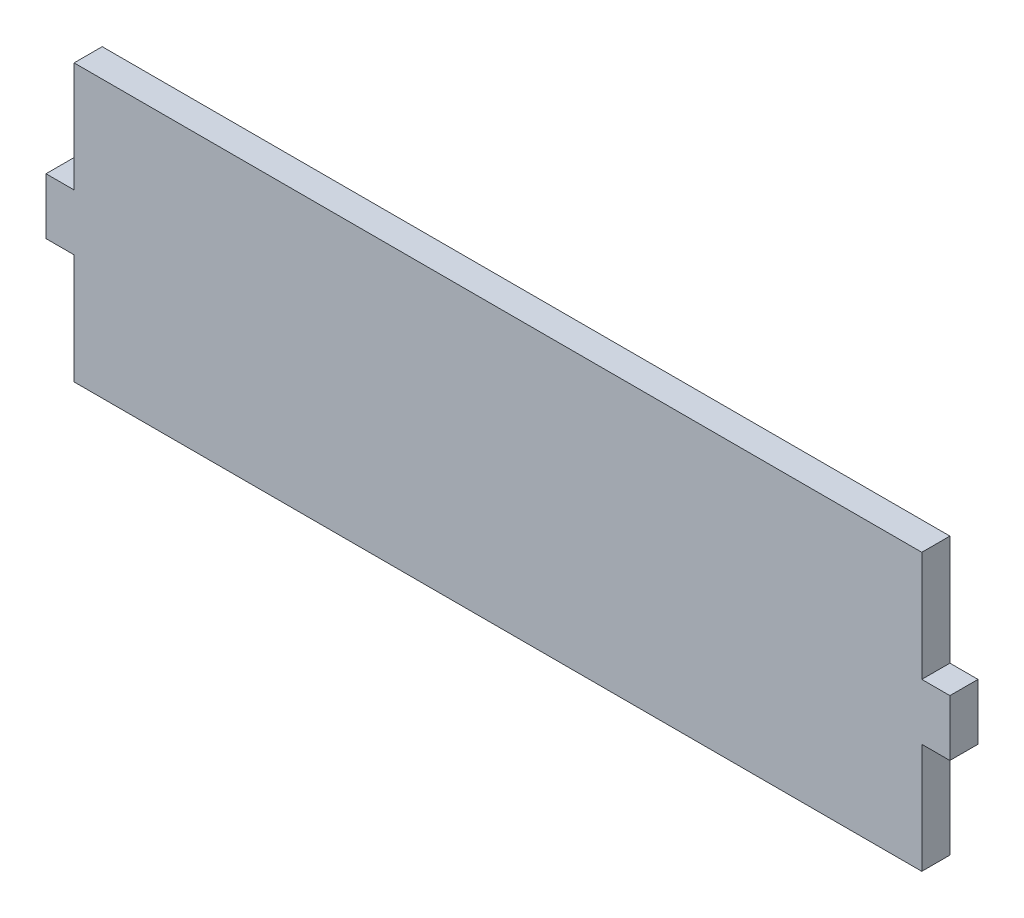
SolidWorks part; units mm, degrees
ref_plane "Front Plane" through (0, 0, 0) normal (0, 0, 1) x (1, 0, 0)
ref_plane "Top Plane" through (0, 0, 0) normal (0, 1, 0) x (1, 0, 0)
ref_plane "Right Plane" through (0, 0, 0) normal (1, 0, 0) x (0, 0, -1)
sketch "Sketch2" plane through (0, 0, 0) normal (0, 1, 0) x (1, 0, 0)
  line L0 (0, 0) -> (0, 6) construction
  dimension "D1" = 6
sketch "Sketch1" plane through (0, 0, 0) normal (0, 0, 1) x (1, 0, 0)
  line L1 (-96.5, -29.5) -> (96.5, -29.5)
  line L2 (-96.5, -29.5) -> (-96.5, 29.5)
  line L3 (-96.5, 29.5) -> (96.5, 29.5)
  line L4 (96.5, -29.5) -> (96.5, 29.5)
  line L5 (-96.5, -29.5) -> (96.5, 29.5) construction
  line L6 (-96.5, 29.5) -> (96.5, -29.5) construction
  line L7 (-96.5, 29.5) -> (-90.5, 29.5)
  line L8 (-96.5, 29.5) -> (-96.5, 6)
  line L9 (-96.5, 6) -> (-90.5, 6)
  line L10 (-90.5, 29.5) -> (-90.5, 6)
  line L11 (-90.5, -29.5) -> (-96.5, -29.5)
  line L12 (-90.5, -29.5) -> (-90.5, -6)
  line L13 (-90.5, -6) -> (-96.5, -6)
  line L14 (-96.5, -29.5) -> (-96.5, -6)
  line L15 (96.5, 29.5) -> (90.5, 29.5)
  line L16 (96.5, 29.5) -> (96.5, 6)
  line L17 (96.5, 6) -> (90.5, 6)
  line L18 (90.5, 29.5) -> (90.5, 6)
  line L19 (96.5, -29.5) -> (90.5, -29.5)
  line L20 (96.5, -29.5) -> (96.5, -6)
  line L21 (96.5, -6) -> (90.5, -6)
  line L22 (90.5, -29.5) -> (90.5, -6)
  point P0 (0, 0)
  dimension "D1" = 193
  dimension "D2" = 59
  dimension "D3" = 12
  dimension "D4" = 6
extrude "Boss-Extrude1" add sketch "Sketch1" against normal up to vertex (6 mm away) contours L1 L22 L21 L4 L17 L18 L3 L10 L9 L2 L13 L12 region at (0, 0, 0) up to point (0, 0, -6)
equation "\"t_wood\"= 6' Thickness of the wood"
equation "\"t_glass\"= 2.5'Thickness of glass panels"
equation "\"w_glass\"= 181"
equation "\"h_glass\"= 151"
equation "\"h_food_internal\" = 60"
equation "\"entry_height\"= 20"
equation "\"entry diameter\"= 8"
equation "\"glass_bottom_overlap\"= 8"
equation "\"default_finger_size\"= 12"
equation "\"brood_depth\"= 42"
equation "\"outer_box_depth\" = \"brood_depth\" + ( 2 * \"t_glass\" ) + ( 2 * \"t_wood\" )"
equation "\"outer_box_width\"= \"w_glass\" + ( 2 * \"t_wood\" )"
equation "\"food_top_clearance\"= 10"
equation "\"outer_box_height\"= \"t_wood\" + \"h_glass\" + \"t_wood\" + \"h_food_internal\" + \"food_top_clearance\" + \"t_wood\""
equation "\"food_internal_depth\"= \"brood_depth\" + \"t_glass\" + \"t_glass\" - \"t_wood\" - \"t_wood\""
equation "\"food_channel_clearance_width\"= 14"
equation "\"bar_top_play\"= 0.5"
equation "\"bar_entry_angle\"= 10"
equation "\"bar_width\"= 20"
equation "\"entry_disk_play\"= 0.3"
equation "\"D1@Sketch2\"=\"t_wood\""
equation "\"D1@Sketch1\"=\"outer_box_width\""
equation "\"D2@Sketch1\"=\"outer_box_depth\""
equation "\"D3@Sketch1\"=\"default_finger_size\""
equation "\"D4@Sketch1\"=\"t_wood\""
